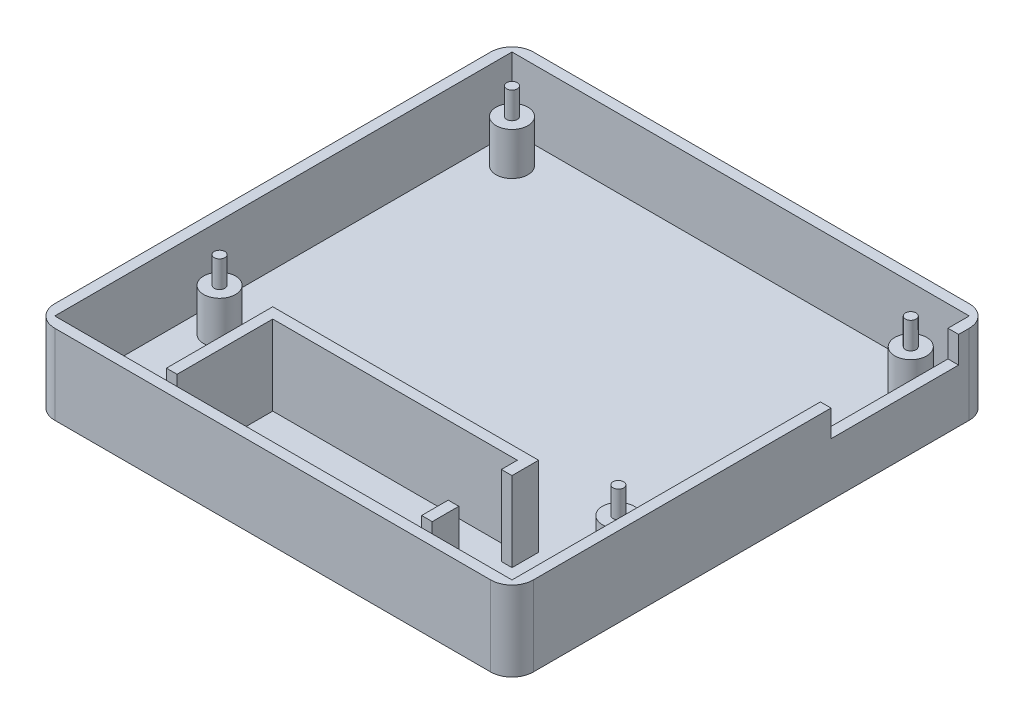
SolidWorks part; units mm, degrees
ref_plane "Front Plane" through (0, 0, 0) normal (0, 0, 1) x (1, 0, 0)
ref_plane "Top Plane" through (0, 0, 0) normal (0, 1, 0) x (1, 0, 0)
ref_plane "Right Plane" through (0, 0, 0) normal (1, 0, 0) x (0, 0, -1)
sketch "Sketch1" plane through (0, 0, 0) normal (0, 1, 0) x (1, 0, 0)
  line L1 (0, 0) -> (90, 0)
  line L2 (0, 0) -> (0, 90)
  line L3 (0, 90) -> (90, 90)
  line L4 (90, 0) -> (90, 90)
  dimension "D1" = 90
  dimension "D2" = 90
extrude "Boss-Extrude1" add sketch "Sketch1" along normal blind 15
sketch "Sketch2" plane through (90, 0, 0) normal (1, 0, 0) x (0, 0, -1)
  line L0 (0, 15) -> (90, 15) construction
  line L1 (60, 15) -> (84, 15)
  line L2 (60, 15) -> (60, 10)
  line L3 (60, 10) -> (84, 10)
  line L4 (84, 15) -> (84, 10)
  line L5 (90, 15) -> (90, 0) construction
  point P8 (72, 10)
  dimension "D1" = 6
  dimension "D2" = 30
  dimension "D3" = 5
extrude "Cut-Extrude1" cut sketch "Sketch2" against normal blind 10
shell "Shell1" thickness 2 removed face at (85, 12.5, -84) removed face at (85, 12.5, -60) removed face at (65, 15, -58.5) removed face at (85, 10, -72) removed face at (80, 12.5, -72)
sketch "Sketch3" plane through (0, 2, 0) normal (0, 1, 0) x (1, 0, 0)
  line L0 (0, 90) -> (0, 0) construction
  line L1 (90, 90) -> (0, 90) construction
  line L2 (45, 88) -> (45, 2) construction
  line L3 (88, 88) -> (2, 88) construction
  line L4 (2, 2) -> (88, 2) construction
  line L5 (0, 0) -> (90, 0) construction
  circle A0 centre (7.5, 82.5) radius 3
  circle A1 centre (82.5, 82.5) radius 3
  circle A2 centre (7.5, 27.5) radius 3
  circle A4 centre (82.5, 27.5) radius 3
  dimension "D1" = 6
  dimension "D4" = 6
  dimension "D2" = 7.5
  dimension "D3" = 7.5
  dimension "D5" = 7.5
  dimension "D6" = 27.5
extrude "Boss-Extrude3" add sketch "Sketch3" along normal blind 8
sketch "Sketch4" plane through (0, 10, 0) normal (0, 1, 0) x (1, 0, 0)
  circle A0 centre (7.5, 27.5) radius 1
  circle A1 centre (7.5, 82.5) radius 1
  circle A2 centre (82.5, 27.5) radius 1
  circle A3 centre (82.5, 82.5) radius 1
  dimension "D1" = 2
  dimension "D2" = 2
extrude "Boss-Extrude4" add sketch "Sketch4" along normal blind 5
fillet "Fillet1" radius 4 4 edges at (0, 7.5, 0) (0, 7.5, -90) (90, 7.5, -90) (90, 7.5, 0)
sketch "Sketch5" plane through (0, 2, 0) normal (0, 1, 0) x (1, 0, 0)
  line L0 (2, 2) -> (88, 2) construction
  line L1 (23, 2) -> (73, 2)
  line L2 (23, 2) -> (23, 22)
  line L3 (23, 22) -> (73, 22)
  line L4 (73, 2) -> (73, 22)
  line L5 (88, 2) -> (88, 88) construction
  point P6 (48, 2)
  dimension "D1" = 20
  dimension "D2" = 15
  dimension "D3" = 50
extrude "Boss-Extrude5" add sketch "Sketch5" along normal blind 15
sketch "Sketch6" plane through (73, 0, 0) normal (1, 0, 0) x (0, 0, -1)
  line L0 (2, 2) -> (22, 2) construction
  line L1 (17, 2) -> (7, 2)
  line L2 (17, 2) -> (17, 17)
  line L3 (17, 17) -> (7, 17)
  line L4 (7, 2) -> (7, 17)
  line L5 (2, 17) -> (22, 17) construction
  line L6 (22, 17) -> (22, 2) construction
  dimension "D1" = 10
  dimension "D2" = 5
extrude "Cut-Extrude2" cut sketch "Sketch6" against normal blind 5
shell "Shell3" thickness 2 removed face at (70.5, 9.5, -7) removed face at (70.5, 9.5, -17) removed face at (68, 9.5, -12) removed face at (59.25, 17, -12) removed face at (48, 16, -2)
